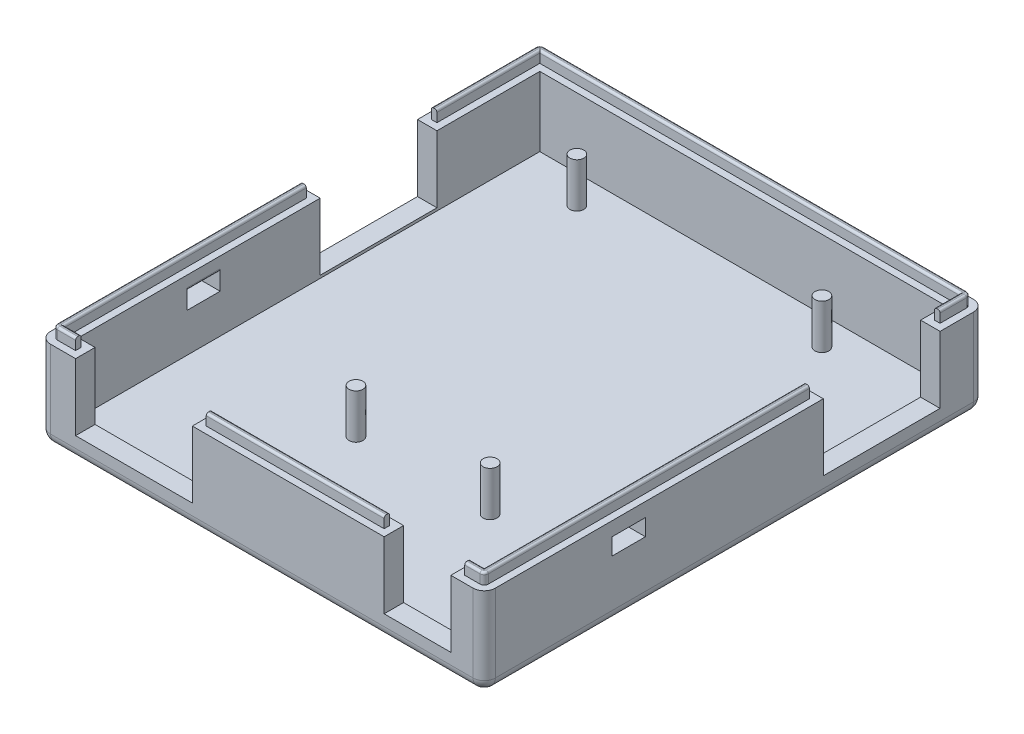
SolidWorks part; units mm, degrees
material "ABS"
ref_plane "Alzado" through (0, 0, 0) normal (0, 0, 1) x (1, 0, 0)
ref_plane "Planta" through (0, 0, 0) normal (0, 1, 0) x (1, 0, 0)
ref_plane "Vista lateral" through (0, 0, 0) normal (1, 0, 0) x (0, 0, -1)
sketch "Croquis1" plane through (0, 0, 0) normal (0, 1, 0) x (1, 0, 0)
  line L1 (-40, 45) -> (40, 45)
  line L2 (-40, 45) -> (-40, -45)
  line L3 (-40, -45) -> (40, -45)
  line L4 (40, 45) -> (40, -45)
  line L5 (-40, 45) -> (40, -45) construction
  line L6 (-40, -45) -> (40, 45) construction
  point P0 (0, 0)
  dimension "D1" = 90
  dimension "D2" = 80
extrude "Saliente-Extruir1" add sketch "Croquis1" along normal blind 28
fillet "Redondeo1" radius 2 12 edges at (0, 28, -45) (40, 28, 0) (0, 28, 45) (-40, 28, 0) (0, 0, 45) (0, 0, -45) (40, 0, 0) (-40, 0, 0) (-40, 14, 45) (40, 14, 45) (40, 14, -45) (-40, 14, -45)
shell "Vaciado2" thickness 3.5
sketch "Croquis3" plane through (0, 0, 45) normal (0, 0, 1) x (1, 0, 0)
  line L1 (-33.5, 18) -> (-12.5, 18)
  line L2 (-33.5, 18) -> (-33.5, 4)
  line L3 (-33.5, 4) -> (-12.5, 4)
  line L4 (-12.5, 18) -> (-12.5, 4)
  line L5 (40, 28) -> (40, 0) construction
  line L6 (22, 18) -> (34, 18)
  line L7 (22, 18) -> (22, 4)
  line L8 (22, 4) -> (34, 4)
  line L9 (34, 18) -> (34, 4)
  line L10 (-40, 28) -> (-40, 0) construction
  line L11 (-38, 2) -> (38, 2) construction
  line L12 (-6.5, 23) -> (9.5, 23)
  line L13 (-6.5, 23) -> (-6.5, 17)
  line L14 (-6.5, 17) -> (9.5, 17)
  line L15 (9.5, 23) -> (9.5, 17)
  dimension "D1" = 14
  dimension "D2" = 12
  dimension "D3" = 6
  dimension "D4" = 6.5
  dimension "D5" = 21
  dimension "D6" = 14
  dimension "D7" = 6
  dimension "D8" = 6
  dimension "D9" = 16
  dimension "D10" = 2
  dimension "D11" = 15
sketch "Croquis4" plane through (-40, 0, 0) normal (-1, 0, 0) x (0, 0, 1)
  line L1 (-23, 18) -> (-2, 18)
  line L2 (-23, 18) -> (-23, 4)
  line L3 (-23, 4) -> (-2, 4)
  line L4 (-2, 18) -> (-2, 4)
  line L5 (-45, 28) -> (-45, 0) construction
  line L6 (45, 28) -> (45, 0) construction
  line L7 (-43, 2) -> (43, 2) construction
  dimension "D1" = 14
  dimension "D2" = 21
  dimension "D3" = 22
  dimension "D4" = 47
  dimension "D5" = 2
sketch "Croquis5" plane through (40, 0, 0) normal (1, 0, 0) x (0, 0, -1)
  line L0 (-43, 2) -> (43, 2) construction
  line L1 (16, 18) -> (37, 18)
  line L2 (16, 18) -> (16, 4)
  line L3 (16, 4) -> (37, 4)
  line L4 (37, 18) -> (37, 4)
  line L5 (45, 28) -> (45, 0) construction
  dimension "D1" = 14
  dimension "D2" = 8
  dimension "D3" = 21
  dimension "D4" = 2
sketch "Croquis6" plane through (0, 3.5, 0) normal (0, 1, 0) x (1, 0, 0)
  line L2 (0, 0) -> (0, 18.5567) construction
  line L3 (0, 0) -> (-1.7547, 0) construction
  circle A8 centre (-24.776, 36.449) radius 1.25
  circle A9 centre (19.304, 36.449) radius 1.25
  circle A10 centre (-8.636, -19.431) radius 1.25
  circle A11 centre (15.494, -19.431) radius 1.25
  dimension "D1" = 2.5
  dimension "D2" = 36.449
  dimension "D3" = 24.776
  dimension "D5" = 19.431
  dimension "D4" = 44.08
  dimension "D6" = 8.636
  dimension "D7" = 24.13
extrude "Saliente-Extruir2" add sketch "Croquis6" along normal blind 8
extrude "Cortar-Extruir1" cut sketch "Croquis3" against normal up to next
extrude "Cortar-Extruir2" cut sketch "Croquis4" against normal up to next
extrude "Cortar-Extruir3" cut sketch "Croquis5" against normal up to next
ref_plane "Plano1" through (0, 16, 0) normal (0, 1, 0) x (1, 0, 0)
split "Partir1" trim tools "Plano1" bodies to split 112 resulting bodies 113 114
sketch "Croquis7" plane through (40, 0, 0) normal (1, 0, 0) x (0, 0, -1)
  line L0 (-19, 16) -> (-19, 12) construction
  line L1 (-43, 16) -> (16, 16) construction
  line L3 (-43, 16) -> (-43, 2) construction
  line L5 (-22, 13.5) -> (-16, 13.5)
  line L6 (-22, 13.5) -> (-22, 10.5)
  line L7 (-22, 10.5) -> (-16, 10.5)
  line L8 (-16, 13.5) -> (-16, 10.5)
  line L9 (-22, 13.5) -> (-16, 10.5) construction
  line L10 (-22, 10.5) -> (-16, 13.5) construction
  dimension "D1" = 24
  dimension "D2" = 3
  dimension "D3" = 6
  dimension "D4" = 4
extrude "Cortar-Extruir4" cut sketch "Croquis7" against normal up to next (3.5 mm away)
ref_plane "Plano2" through (0, 0, 21.5) normal (0, 0, -1) x (-1, 0, 0)
sketch "Croquis9" plane through (0, 0, 21.5) normal (0, 0, -1) x (-1, 0, 0)
  line L0 (-40.5, 13.5) -> (-36.5, 13.5)
  line L1 (-36.5, 13.5) -> (-36.5, 21.5)
  line L2 (-36.5, 16) -> (-36.5, 3.5) construction
  line L3 (-36.5, 21.5) -> (-34.5, 21.5)
  line L4 (-34.5, 21.5) -> (-34.5, 11.5)
  line L5 (-34.5, 11.5) -> (-40.5, 11.5)
  line L7 (-40.5, 11.5) -> (-40.5, 13.5)
  dimension "D1" = 2
  dimension "D2" = 2
  dimension "D3" = 10
  dimension "D4" = 6
extrude "Saliente-Extruir3" add sketch "Croquis9" along normal blind 5
chamfer "Chaflán1" distance 2 angle 45 1 edges at (40.5, 11.5, 19)
chamfer "Chaflán2" distance 1 angle 45 1 edges at (40.5, 13.5, 19)
chamfer "Chaflán3" distance 2 angle 45 1 edges at (34.5, 21.5, 19)
fillet "Redondeo2" radius 0.5 1 edges at (36.5, 13.5, 19)
fillet "Redondeo3" radius 0.5 1 edges at (36.5, 13.5, 19)
mirror "Simetría2" about plane through (0, 0, 0) normal (1, 0, 0) of "Cortar-Extruir4"
fillet "Redondeo4" radius 0.5 1 edges at (-36.5, 13.5, 19)
mirror "Simetría3" about plane through (0, 0, 0) normal (1, 0, 0) of "Redondeo2", "Chaflán3", "Chaflán2", "Chaflán1", "Saliente-Extruir3"
sketch "Croquis10" plane through (0, 16, 0) normal (0, 1, 0) x (1, 0, 0)
  line L24 (-38.75, 43) -> (-38.75, 24.25)
  line L25 (-38.75, 24.25) -> (-37.75, 24.25)
  line L26 (-37.75, 24.25) -> (-37.75, 42.75)
  line L27 (-37.75, 42.75) -> (37.75, 42.75)
  line L28 (37.75, 42.75) -> (37.75, 38.25)
  line L29 (37.75, 38.25) -> (38.75, 38.25)
  line L30 (38.75, 38.25) -> (38.75, 43)
  line L31 (38, 43.75) -> (-38, 43.75)
  line L32 (-38.75, 43) -> (-38.75, 24.25)
  line L33 (-38.75, 24.25) -> (-37.75, 24.25)
  line L34 (-37.75, 24.25) -> (-37.75, 42.75)
  line L35 (-37.75, 42.75) -> (37.75, 42.75)
  line L36 (37.75, 42.75) -> (37.75, 38.25)
  line L37 (37.75, 38.25) -> (38.75, 38.25)
  line L38 (38.75, 38.25) -> (38.75, 43)
  line L39 (38, 43.75) -> (-38, 43.75)
  line L44 (37.75, -42.75) -> (35.25, -42.75)
  line L45 (35.25, -42.75) -> (35.25, -43.75)
  line L46 (35.25, -43.75) -> (38, -43.75)
  line L47 (38.75, -43) -> (38.75, 14.75)
  line L48 (38.75, 14.75) -> (37.75, 14.75)
  line L49 (37.75, 14.75) -> (37.75, -42.75)
  line L50 (37.75, -42.75) -> (35.25, -42.75)
  line L51 (35.25, -42.75) -> (35.25, -43.75)
  line L52 (35.25, -43.75) -> (38, -43.75)
  line L53 (38.75, -43) -> (38.75, 14.75)
  line L54 (38.75, 14.75) -> (37.75, 14.75)
  line L55 (37.75, 14.75) -> (37.75, -42.75)
  line L58 (20.75, -42.75) -> (-11.25, -42.75)
  line L59 (-11.25, -42.75) -> (-11.25, -43.75)
  line L60 (-11.25, -43.75) -> (20.75, -43.75)
  line L61 (20.75, -43.75) -> (20.75, -42.75)
  line L62 (20.75, -42.75) -> (-11.25, -42.75)
  line L63 (-11.25, -42.75) -> (-11.25, -43.75)
  line L64 (-11.25, -43.75) -> (20.75, -43.75)
  line L65 (20.75, -43.75) -> (20.75, -42.75)
  line L74 (-34.75, -42.75) -> (-37.75, -42.75)
  line L75 (-37.75, -42.75) -> (-37.75, 0.75)
  line L76 (-37.75, 0.75) -> (-38.75, 0.75)
  line L77 (-38.75, 0.75) -> (-38.75, -43)
  line L78 (-38, -43.75) -> (-34.75, -43.75)
  line L79 (-34.75, -43.75) -> (-34.75, -42.75)
  line L80 (-34.75, -42.75) -> (-37.75, -42.75)
  line L81 (-37.75, -42.75) -> (-37.75, 0.75)
  line L82 (-37.75, 0.75) -> (-38.75, 0.75)
  line L83 (-38.75, 0.75) -> (-38.75, -43)
  line L84 (-38, -43.75) -> (-34.75, -43.75)
  line L85 (-34.75, -43.75) -> (-34.75, -42.75)
  arc A6 (-38, 43.75) -> (-38.75, 43) centre (-38, 43) ccw
  arc A7 (38.75, 43) -> (38, 43.75) centre (38, 43) ccw
  arc A8 (-38, 43.75) -> (-38.75, 43) centre (-38, 43) ccw
  arc A9 (38.75, 43) -> (38, 43.75) centre (38, 43) ccw
  arc A10 (38, -43.75) -> (38.75, -43) centre (38, -43) ccw
  arc A11 (38, -43.75) -> (38.75, -43) centre (38, -43) ccw
  arc A13 (-38.75, -43) -> (-38, -43.75) centre (-38, -43) ccw
  arc A14 (-38.75, -43) -> (-38, -43.75) centre (-38, -43) ccw
  dimension "D1" = 1.25
  dimension "D2" = 1.25
  dimension "D3" = 1.25
  dimension "D4" = 1.25
extrude "Saliente-Extruir4" add sketch "Croquis10" along normal blind 2
fillet "Redondeo6" radius 0.4 20 edges at (-38.75, 18, 21.125) (-38.5303, 18, 43.5303) (36.625, 18, 43.75) (38.5303, 18, 43.5303) (36.5, 18, 42.75) (-36.25, 18, 42.75) (-37.75, 18, 21) (-36.375, 18, 43.75) (4.75, 18, 42.75) (4.75, 18, 43.75) (37.75, 18, 14) (38.75, 18, 14.125) (-38.75, 18, -33.625) (-38.5303, 18, -43.5303) (0, 18, -43.75) (38.5303, 18, -43.5303) (-37.75, 18, -33.5) (37.75, 18, -40.5) (38.75, 18, -40.625) (0, 18, -42.75)
sketch "Croquis11" plane through (0, 16, 0) normal (0, -1, 0) x (1, 0, 0)
  line L16 (35, 42.5) -> (37.5, 42.5)
  line L17 (37.5, 42.5) -> (37.5, 21.5)
  line L18 (37.5, 21.5) -> (37.5, 16.5)
  line L19 (37.5, 16.5) -> (37.5, -15)
  line L20 (37.5, -15) -> (39, -15)
  line L21 (39, -15) -> (39, 43)
  line L22 (38, 44) -> (35, 44)
  line L23 (35, 44) -> (35, 42.5)
  line L24 (35, 42.5) -> (37.5, 42.5)
  line L25 (37.5, 42.5) -> (37.5, 21.5)
  line L26 (37.5, 21.5) -> (37.5, 16.5)
  line L27 (37.5, 16.5) -> (37.5, -15)
  line L28 (37.5, -15) -> (39, -15)
  line L29 (39, -15) -> (39, 43)
  line L30 (38, 44) -> (35, 44)
  line L31 (35, 44) -> (35, 42.5)
  line L32 (-11.5, 42.5) -> (21, 42.5)
  line L33 (21, 42.5) -> (21, 44)
  line L34 (21, 44) -> (-11.5, 44)
  line L35 (-11.5, 44) -> (-11.5, 42.5)
  line L36 (-11.5, 42.5) -> (21, 42.5)
  line L37 (21, 42.5) -> (21, 44)
  line L38 (21, 44) -> (-11.5, 44)
  line L39 (-11.5, 44) -> (-11.5, 42.5)
  line L44 (-37.5, 42.5) -> (-34.5, 42.5)
  line L45 (-34.5, 42.5) -> (-34.5, 44)
  line L46 (-34.5, 44) -> (-38, 44)
  line L47 (-39, 43) -> (-39, -1)
  line L48 (-39, -1) -> (-37.5, -1)
  line L49 (-37.5, -1) -> (-37.5, 16.5)
  line L50 (-37.5, 16.5) -> (-37.5, 21.5)
  line L51 (-37.5, 21.5) -> (-37.5, 42.5)
  line L52 (-37.5, 42.5) -> (-34.5, 42.5)
  line L53 (-34.5, 42.5) -> (-34.5, 44)
  line L54 (-34.5, 44) -> (-38, 44)
  line L55 (-39, 43) -> (-39, -1)
  line L56 (-39, -1) -> (-37.5, -1)
  line L57 (-37.5, -1) -> (-37.5, 16.5)
  line L58 (-37.5, 16.5) -> (-37.5, 21.5)
  line L59 (-37.5, 21.5) -> (-37.5, 42.5)
  line L68 (-38, -44) -> (38, -44)
  line L69 (39, -43) -> (39, -38)
  line L70 (39, -38) -> (37.5, -38)
  line L71 (37.5, -38) -> (37.5, -42.5)
  line L72 (37.5, -42.5) -> (-37.5, -42.5)
  line L73 (-37.5, -42.5) -> (-37.5, -24)
  line L74 (-37.5, -24) -> (-39, -24)
  line L75 (-39, -24) -> (-39, -43)
  line L76 (-38, -44) -> (38, -44)
  line L77 (39, -43) -> (39, -38)
  line L78 (39, -38) -> (37.5, -38)
  line L79 (37.5, -38) -> (37.5, -42.5)
  line L80 (37.5, -42.5) -> (-37.5, -42.5)
  line L81 (-37.5, -42.5) -> (-37.5, -24)
  line L82 (-37.5, -24) -> (-39, -24)
  line L83 (-39, -24) -> (-39, -43)
  arc A2 (39, 43) -> (38, 44) centre (38, 43) ccw
  arc A3 (39, 43) -> (38, 44) centre (38, 43) ccw
  arc A4 (-38, 44) -> (-39, 43) centre (-38, 43) ccw
  arc A5 (-38, 44) -> (-39, 43) centre (-38, 43) ccw
  arc A9 (-39, -43) -> (-38, -44) centre (-38, -43) ccw
  arc A10 (38, -44) -> (39, -43) centre (38, -43) ccw
  arc A11 (-39, -43) -> (-38, -44) centre (-38, -43) ccw
  arc A12 (38, -44) -> (39, -43) centre (38, -43) ccw
  dimension "D1" = 1
  dimension "D2" = 1
  dimension "D3" = 1
  dimension "D4" = 1
extrude "Cortar-Extruir5" cut sketch "Croquis11" against normal blind 2.5
fillet "Redondeo7" radius 0.4 36 edges at (-6.5, 17.75, 42.5) (-6.5, 17.75, 44) (9.5, 17.75, 44) (9.5, 17.75, 42.5) (39, 18.5, -40.5) (38.7071, 18.5, -43.7071) (0, 18.5, -44) (-38.7071, 18.5, -43.7071) (-39, 18.5, 21) (-38.7071, 18.5, 43.7071) (-9, 18.5, 42.5) (-11.5, 18.5, 43.25) (-9, 18.5, 44) (-6.5, 18.5, 43.25) (15.25, 18.5, 44) (21, 18.5, 43.25) (15.25, 18.5, 42.5) (9.5, 18.5, 43.25) (36.5, 18.5, 44) (38.7071, 18.5, 43.7071) (39, 18.5, 14) (38.25, 18.5, -15) (37.5, 18.5, 13.75) (36.25, 18.5, 42.5) (35, 18.5, 43.25) (38.25, 18.5, -38) (37.5, 18.5, -40.25) (0, 18.5, -42.5) (-39, 18.5, -33.5) (-37.5, 18.5, -33.25) (-38.25, 18.5, -24) (-38.25, 18.5, -1) (-36.25, 18.5, 44) (-34.5, 18.5, 43.25) (-36, 18.5, 42.5) (-37.5, 18.5, 20.75)
sketch "Croquis12" plane through (0, 28, 0) normal (0, 1, 0) x (1, 0, 0)
  line L0 (38, -43) -> (38, 43) construction
  line L1 (12.1, -26.7) -> (22.5, -26.7)
  line L2 (12.1, -26.7) -> (12.1, -37.5)
  line L3 (12.1, -37.5) -> (22.5, -37.5)
  line L4 (22.5, -26.7) -> (22.5, -37.5)
  line L5 (36.5, -41.5) -> (-36.5, -41.5) construction
  line L6 (-38, 43) -> (-38, -43) construction
  line L7 (-30.5, 27.5) -> (-19.7, 27.5)
  line L8 (-30.5, 27.5) -> (-30.5, 22.5)
  line L9 (-30.5, 22.5) -> (-19.7, 22.5)
  line L10 (-19.7, 27.5) -> (-19.7, 22.5)
  line L11 (38, 43) -> (-38, 43) construction
  dimension "D1" = 10.4
  dimension "D2" = 10.8
  dimension "D3" = 15.5
  dimension "D4" = 4
  dimension "D5" = 10.8
  dimension "D6" = 5
  dimension "D7" = 7.5
  dimension "D8" = 15.5
extrude "Cortar-Extruir6" cut sketch "Croquis12" against normal up to next (3.5 mm away)
sketch "Croquis13" plane through (0, 28, 0) normal (0, 1, 0) x (1, 0, 0)
  line L0 (0, 34.8306) -> (0, -34.8306) construction
  text T0 "CONVEYOR  BOX\r\n1.0" font "Helvetica Rounded" height 3.5
  point P4 (0, 0)
extrude "Cortar-Extruir7" cut sketch "Croquis13" against normal blind 1.5
delete or keep bodies "Sólido-Eliminar/Conservar 1" type delete bodies bodies 128
